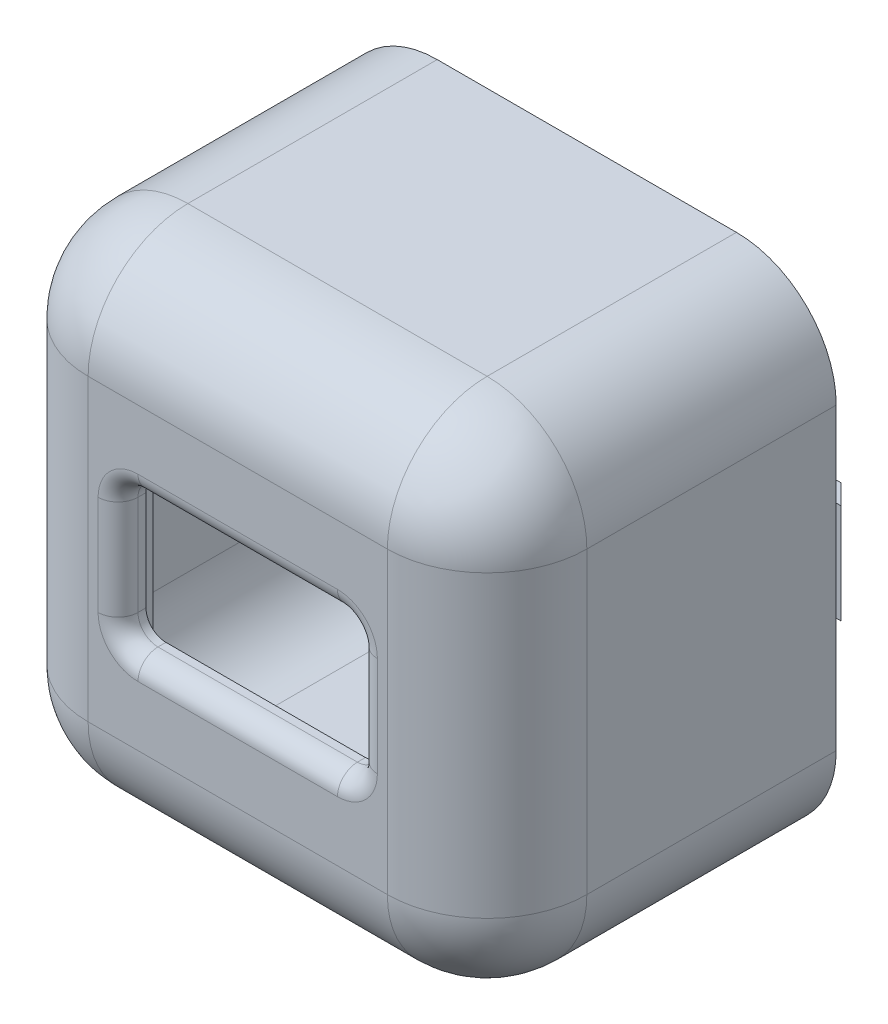
SolidWorks part; units mm, degrees
ref_plane "Front Plane" through (0, 0, 0) normal (0, 0, 1) x (1, 0, 0)
ref_plane "Top Plane" through (0, 0, 0) normal (0, 1, 0) x (1, 0, 0)
ref_plane "Right Plane" through (0, 0, 0) normal (1, 0, 0) x (0, 0, -1)
sketch "Sketch1" plane through (0, 0, 0) normal (0, 0, 1) x (1, 0, 0)
  line L1 (-25, -25) -> (25, -25)
  line L2 (-25, -25) -> (-25, 25)
  line L3 (-25, 25) -> (25, 25)
  line L4 (25, -25) -> (25, 25)
  line L5 (-25, -25) -> (25, 25) construction
  line L6 (-25, 25) -> (25, -25) construction
  point P0 (0, 0)
  dimension "D1" = 50
  dimension "D2" = 50
extrude "Boss-Extrude1" add sketch "Sketch1" along normal blind 45
fillet "Fillet1" radius 10 8 edges at (0, -25, 45) (-25, 0, 45) (0, 25, 45) (25, 0, 45) (-25, -25, 22.5) (25, -25, 22.5) (25, 25, 22.5) (-25, 25, 22.5)
shell "Shell1" thickness 2 removed face at (0, 0, 0)
sketch "Sketch2" plane through (0, 0, 43) normal (0, 0, -1) x (-1, 0, 0)
  line L1 (-12, -7) -> (12, -7)
  line L2 (-12, -7) -> (-12, 7)
  line L3 (-12, 7) -> (12, 7)
  line L4 (12, -7) -> (12, 7)
  line L5 (-12, -7) -> (12, 7) construction
  line L6 (-12, 7) -> (12, -7) construction
  point P0 (0, 0)
  dimension "D1" = 24
  dimension "D2" = 14
extrude "Cut-Extrude1" cut sketch "Sketch2" against normal blind 10
sketch "Sketch3" plane through (0, 0, 43) normal (0, 0, -1) x (-1, 0, 0)
  line L26 (14, -9) -> (14, 9)
  line L27 (-14, -9) -> (14, -9)
  line L28 (-14, 9) -> (-14, -9)
  line L29 (14, 9) -> (-14, 9)
  line L30 (14, -9) -> (14, 9)
  line L31 (-14, -9) -> (14, -9)
  line L32 (-14, 9) -> (-14, -9)
  line L33 (14, 9) -> (-14, 9)
  dimension "D2" = 2
extrude "Boss-Extrude2" add sketch "Sketch3" along normal blind 2
sketch "Sketch4" plane through (0, 0, 43) normal (0, 0, 1) x (1, 0, 0)
  line L4 (12, 7) -> (-12, 7)
  line L6 (12, 7) -> (-12, 7)
  line L12 (-12, 7) -> (-12, -7)
  line L14 (-12, 7) -> (-12, -7)
  line L16 (-12, -7) -> (12, -7)
  line L17 (-12, -7) -> (12, -7)
  line L18 (12, -7) -> (12, 7)
  line L19 (12, -7) -> (12, 7)
  dimension "D1" = 0
extrude "Cut-Extrude2" cut sketch "Sketch4" against normal blind 2
fillet "Fillet2" radius 2 4 edges at (12, 7, 43) (12, -7, 43) (-12, -7, 43) (-12, 7, 43)
fillet "Fillet3" radius 2 8 edges at (-11.4142, -6.4142, 45) (0, -7, 45) (11.4142, -6.4142, 45) (12, 0, 45) (11.4142, 6.4142, 45) (0, 7, 45) (-11.4142, 6.4142, 45) (-12, 0, 45)
sketch "Sketch5" plane through (0, 0, 41) normal (0, 0, -1) x (-1, 0, 0)
  line L1 (-14, -14) -> (14, -14)
  line L2 (-14, -14) -> (-14, 14)
  line L3 (-14, 14) -> (14, 14)
  line L4 (14, -14) -> (14, 14)
  line L5 (-14, -14) -> (14, 14) construction
  line L6 (-14, 14) -> (14, -14) construction
  point P0 (0, 0)
  dimension "D1" = 28
  dimension "D2" = 28
extrude "Boss-Extrude3" add sketch "Sketch5" against normal blind 2
sketch "Sketch7" plane through (0, 0, 43) normal (0, 0, 1) x (1, 0, 0)
  line L4 (12, -5) -> (12, 5)
  line L5 (10, 7) -> (-10, 7)
  line L6 (-12, 5) -> (-12, -5)
  line L7 (-10, -7) -> (10, -7)
  line L8 (12, -5) -> (12, 5)
  line L9 (10, 7) -> (-10, 7)
  line L10 (-12, 5) -> (-12, -5)
  line L11 (-10, -7) -> (10, -7)
  arc A4 (12, 5) -> (10, 7) centre (10, 5) ccw
  arc A5 (-10, 7) -> (-12, 5) centre (-10, 5) ccw
  arc A6 (-12, -5) -> (-10, -7) centre (-10, -5) ccw
  arc A7 (10, -7) -> (12, -5) centre (10, -5) ccw
  arc A8 (12, 5) -> (10, 7) centre (10, 5) ccw
  arc A9 (-10, 7) -> (-12, 5) centre (-10, 5) ccw
  arc A10 (-12, -5) -> (-10, -7) centre (-10, -5) ccw
  arc A11 (10, -7) -> (12, -5) centre (10, -5) ccw
  dimension "D1" = 0
extrude "Cut-Extrude4" cut sketch "Sketch7" against normal blind 2
sketch "Sketch8" plane through (0, 0, 41) normal (0, 0, -1) x (-1, 0, 0)
  line L1 (12.5, 8.5) -> (-12.5, 8.5)
  line L2 (12.5, 8.5) -> (12.5, -8.5)
  line L3 (12.5, -8.5) -> (-12.5, -8.5)
  line L4 (-12.5, 8.5) -> (-12.5, -8.5)
  line L5 (12.5, 8.5) -> (-12.5, -8.5) construction
  line L6 (12.5, -8.5) -> (-12.5, 8.5) construction
  point P0 (0, 0)
  dimension "D1" = 17
  dimension "D2" = 25
extrude "Cut-Extrude5" cut sketch "Sketch8" against normal blind 1.2
sketch "Sketch9" plane through (0, 0, 41) normal (0, 0, -1) x (-1, 0, 0)
  line L0 (-14, -14) -> (14, -14) construction
  line L1 (14, -14) -> (-14, -14)
  line L2 (14, -14) -> (14, -10)
  line L3 (14, -10) -> (-14, -10)
  line L4 (-14, -14) -> (-14, -10)
  line L5 (-14, 14) -> (-14, -14) construction
  dimension "D1" = 4
extrude "Cut-Extrude6" cut sketch "Sketch9" against normal blind 1.2
sketch "Sketch13" plane through (0, 0, 0) normal (0, 0, -1) x (-1, 0, 0)
  line L4 (-15, -25) -> (15, -25)
  line L5 (25, -15) -> (25, 15)
  line L6 (15, 25) -> (-15, 25)
  line L7 (-25, 15) -> (-25, -15)
  line L8 (-15, -25) -> (15, -25)
  line L9 (25, -15) -> (25, 15)
  line L10 (15, 25) -> (-15, 25)
  line L11 (-25, 15) -> (-25, -15)
  arc A4 (15, -25) -> (25, -15) centre (15, -15) ccw
  arc A5 (25, 15) -> (15, 25) centre (15, 15) ccw
  arc A6 (-15, 25) -> (-25, 15) centre (-15, 15) ccw
  arc A7 (-25, -15) -> (-15, -25) centre (-15, -15) ccw
  arc A8 (15, -25) -> (25, -15) centre (15, -15) ccw
  arc A9 (25, 15) -> (15, 25) centre (15, 15) ccw
  arc A10 (-15, 25) -> (-25, 15) centre (-15, 15) ccw
  arc A11 (-25, -15) -> (-15, -25) centre (-15, -15) ccw
  dimension "D1" = 0
extrude "Cut-Extrude10" cut sketch "Sketch13" against normal blind 10
sketch "Sketch14" plane through (-23, 0, 0) normal (1, 0, 0) x (0, 0, -1)
  line L0 (0, 0) -> (-10, 0) construction
  line L1 (-10, -15) -> (-10, 15) construction
  line L3 (-13.5, -5) -> (-6.5, -5)
  line L4 (-13.5, -5) -> (-13.5, 5)
  line L5 (-13.5, 5) -> (-6.5, 5)
  line L6 (-6.5, -5) -> (-6.5, 5)
  line L7 (-13.5, -5) -> (-6.5, 5) construction
  line L8 (-13.5, 5) -> (-6.5, -5) construction
  dimension "D1" = 10
  dimension "D2" = 3.5
extrude "Boss-Extrude4" add sketch "Sketch14" along normal blind 3
sketch "Sketch15" plane through (-23, 0, 0) normal (-1, 0, 0) x (0, 0, 1)
  line L5 (10, -5) -> (6.5, -5) construction
  line L6 (6.5, 5) -> (8.5, 5)
  line L7 (6.5, 5) -> (6.5, -5)
  line L8 (6.5, -5) -> (8.5, -5)
  line L9 (8.5, 5) -> (8.5, -5)
  dimension "D1" = 2
extrude "Boss-Extrude5" add sketch "Sketch15" along normal blind 1
chamfer "Chamfer1" distance 2 angle 45 1 edges at (-24, 0, 6.5)
fillet "Fillet4" radius 1 4 edges at (-23, 0, 13.5) (-23, 5, 11.75) (-23, -5, 11.75) (-20, 0, 13.5)
mirror "Mirror1" about plane through (0, 0, 0) normal (1, 0, 0) of "Chamfer1", "Boss-Extrude5", "Boss-Extrude4"
fillet "Fillet5" radius 1 4 edges at (20, 0, 13.5) (23, 5, 11.75) (23, 0, 13.5) (23, -5, 11.75)
